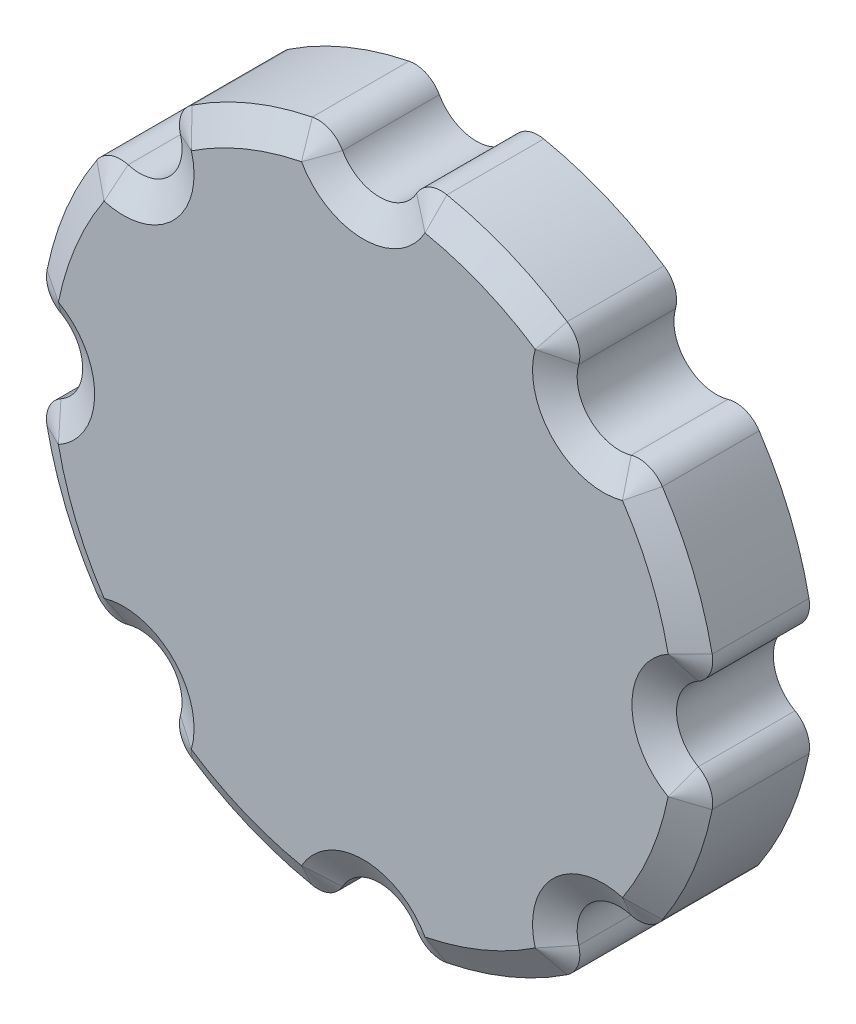
SolidWorks part; units mm, degrees
ref_plane "前视基准面" through (0, 0, 0) normal (0, 0, 1) x (1, 0, 0)
ref_plane "上视基准面" through (0, 0, 0) normal (0, 1, 0) x (1, 0, 0)
ref_plane "右视基准面" through (0, 0, 0) normal (1, 0, 0) x (0, 0, -1)
sketch "草图1" plane through (0, 0, 0) normal (0, 0, 1) x (1, 0, 0)
  circle A0 centre (0, 0) radius 1.5
  circle A1 centre (0, 0) radius 3
  dimension "D1" = 3
  dimension "D2" = 6
extrude "凸台-拉伸1" add sketch "草图1" along normal blind 1
sketch "草图2" plane through (0, 0, 1) normal (0, 0, 1) x (1, 0, 0)
  circle A0 centre (0, 0) radius 6
  dimension "D1" = 12
extrude "凸台-拉伸2" add sketch "草图2" along normal blind 2
sketch "草图3" plane through (0, 0, 3) normal (0, 0, 1) x (1, 0, 0)
  circle A0 centre (0, 6) radius 0.75
  circle A1 centre (0, 0) radius 6 construction
  circle A2 centre (4.2426, 4.2426) radius 0.75
  circle A3 centre (6, 0) radius 0.75
  circle A4 centre (4.2426, -4.2426) radius 0.75
  circle A5 centre (0, -6) radius 0.75
  circle A6 centre (-4.2426, -4.2426) radius 0.75
  circle A7 centre (-6, 0) radius 0.75
  circle A8 centre (-4.2426, 4.2426) radius 0.75
  point P5 (0, 0)
  point P20 (0, 0)
  dimension "D1" = 1.5
  dimension "D2" = 8
extrude "切除-拉伸1" cut sketch "草图3" against normal blind 22
fillet "圆角1" radius 0.5 16 edges at (3.6802, 4.7388, 2) (4.7388, 3.6802, 2) (5.9531, -0.7485, 2) (5.9531, 0.7485, 2) (4.7388, -3.6802, 2) (3.6802, -4.7388, 2) (-0.7485, -5.9531, 2) (0.7485, -5.9531, 2) (-3.6802, -4.7388, 2) (-4.7388, -3.6802, 2) (-5.9531, -0.7485, 2) (-5.9531, 0.7485, 2) (-4.7388, 3.6802, 2) (-3.6802, 4.7388, 2) (-0.7485, 5.9531, 2) (0.7485, 5.9531, 2)
chamfer "倒角1" distance 0.5 angle 30 32 edges at (4.757, 3.5089, 3) (5.5433, 2.2961, 3) (5.8449, 0.8826, 3) (5.25, 0, 3) (5.8449, -0.8826, 3) (5.5433, -2.2961, 3) (4.757, -3.5089, 3) (3.7123, -3.7123, 3) (3.5089, -4.757, 3) (2.2961, -5.5433, 3) (0.8826, -5.8449, 3) (0, -5.25, 3) (-0.8826, -5.8449, 3) (-2.2961, -5.5433, 3) (-3.5089, -4.757, 3) (-3.7123, -3.7123, 3) (-4.757, -3.5089, 3) (-5.5433, -2.2961, 3) (-5.8449, -0.8826, 3) (-5.25, 0, 3) (-5.8449, 0.8826, 3) (-5.5433, 2.2961, 3) (-4.757, 3.5089, 3) (-3.7123, 3.7123, 3) (-3.5089, 4.757, 3) (-2.2961, 5.5433, 3) (-0.8826, 5.8449, 3) (0, 5.25, 3) (0.8826, 5.8449, 3) (2.2961, 5.5433, 3) (3.5089, 4.757, 3) (3.7123, 3.7123, 3) first distance on face at (0, 0, 3)
